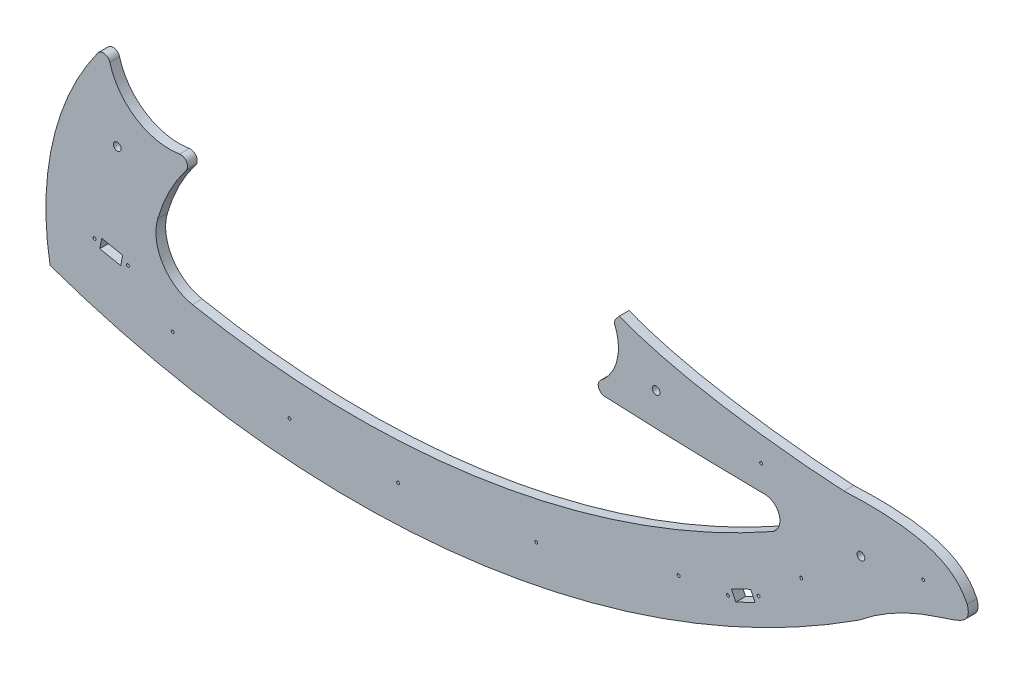
SolidWorks part; units mm, degrees
material "Фанера березовая"
ref_plane "Front Plane" through (0, 0, 0) normal (0, 0, 1) x (1, 0, 0)
ref_plane "Top Plane" through (0, 0, 0) normal (0, 1, 0) x (1, 0, 0)
ref_plane "Right Plane" through (0, 0, 0) normal (1, 0, 0) x (0, 0, -1)
sketch "Несущая боковая" plane through (0, 0, 0) normal (0, 0, 1) x (1, 0, 0)
  line L6 (398.785, -200.6515) -> (-79.2948, -202.7)
  arc A0 (568.0858, 187.1743) -> (604.9253, 231.748) centre (555.0835, 235.431) ccw
  arc A1 (604.9253, 231.748) -> (587.3016, 257.9076) centre (579.4885, 233.6276) ccw
  arc A2 (587.3016, 257.9076) -> (556.344, 256.9224) centre (573.2016, 214.0906) ccw
  arc A4 (-130.7033, -495.9282) -> (-177.7889, -420.4808) centre (-169.1009, -467.4752) ccw
  arc A7 (-130.7033, -495.9282) -> (-181.6944, -712.4375) centre (95.3308, -663.4217) ccw
  arc A8 (-183.8786, -325.353) -> (-177.7889, -420.4808) centre (-186.515, -373.2806) ccw
  arc A9 (-112.9747, -345.6094) -> (-183.8786, -325.353) centre (-193.0224, -491.581) ccw
  arc A11 (23.5507, -511.1423) -> (553.7515, -548.6326) centre (601.0308, 3887.8918) ccw
  arc A12 (7.2112, -514.4863) -> (-70.9864, -615.6156) centre (95.3308, -663.4217) ccw
  arc A13 (-70.9864, -615.6156) -> (-35.2447, -674.0637) centre (-26.3207, -628.4543) ccw
  arc A14 (23.5507, -511.1423) -> (7.2112, -514.4863) centre (20.2245, -536.4807) ccw
  arc A15 (-181.6944, -712.4375) -> (650.1904, -612.5982) centre (132.6498, 184.0228) ccw
  arc A16 (-35.2447, -674.0637) -> (561.2917, -578.0579) centre (132.6498, 184.0228) ccw
  arc A17 (561.2917, -578.0579) -> (553.7515, -548.6326) centre (553.584, -564.3543) ccw
  spline S0 degree 3 poles (556.344, 256.9224) (413.4931, 200.7) (492.8039, -30.4464) (410.7267, -175.5993) knots 0.000401 0.000401 0.000401 0.000401 0.043478 0.043478 0.043478 0.043478
  spline S1 degree 3 poles (410.7267, -175.5993) (407.231, -184.6492) (403.2193, -192.9282) (398.785, -200.6515) knots 0.043478 0.043478 0.043478 0.043478 0.086957 0.086957 0.086957 0.086957
  spline S2 degree 3 poles (-79.2948, -202.7) (-78.5172, -227.7) (-66.7741, -249.7094) (-44.1772, -268.7587) knots 0.130435 0.130435 0.130435 0.130435 0.173913 0.173913 0.173913 0.173913
  spline S3 degree 3 poles (-44.1772, -268.7587) (-12.7058, -245.829) (38.9597, -231.7344) (82.6666, -241.804) knots 0.173913 0.173913 0.173913 0.173913 0.217391 0.217391 0.217391 0.217391
  spline S4 degree 3 poles (82.6666, -241.804) (105.6787, -251.6525) (111.2464, -268.6919) (94.2115, -290.7234) knots 0.217391 0.217391 0.217391 0.217391 0.26087 0.26087 0.26087 0.26087
  spline S5 degree 3 poles (94.2115, -290.7234) (87.1581, -299.8457) (74.9831, -308.4217) (61.0599, -320.5021) knots 0.26087 0.26087 0.26087 0.26087 0.304348 0.304348 0.304348 0.304348
  spline S6 degree 3 poles (61.0599, -320.5021) (47.3806, -331.8412) (34.8832, -345.2678) (22.8705, -359.1067) knots 0.304348 0.304348 0.304348 0.304348 0.347826 0.347826 0.347826 0.347826
  spline S7 degree 3 poles (22.8705, -359.1067) (-5.5844, -391.8897) (-25.5922, -386.6363) (-46.4172, -376.7876) knots 0.347826 0.347826 0.347826 0.347826 0.391304 0.391304 0.391304 0.391304
  spline S8 degree 3 poles (-46.4172, -376.7876) (-71.9902, -366.2219) (-92.784, -356.6815) (-112.9747, -345.6094) knots 0.391304 0.391304 0.391304 0.391304 0.434783 0.434783 0.434783 0.434783
  spline S15 degree 3 poles (650.1904, -612.5982) (721.7263, -555.1366) (771.3742, -572.8028) (761.971, -542.4383) knots 0.695652 0.695652 0.695652 0.695652 0.73913 0.73913 0.73913 0.73913
  spline S16 degree 3 poles (761.971, -542.4383) (749.9881, -518.2511) (723.1034, -500.8362) (635.2399, -505.0064) knots 0.73913 0.73913 0.73913 0.73913 0.782609 0.782609 0.782609 0.782609
  spline S17 degree 3 poles (635.2399, -505.0064) (572.992, -501.9328) (433.5503, -486.7788) (380.9104, -452.9037) knots 0.782609 0.782609 0.782609 0.782609 0.826087 0.826087 0.826087 0.826087
  spline S18 degree 3 poles (380.9104, -452.9037) (364.7659, -442.5143) (356.7862, -430.3638) (361.7026, -416.2609) knots 0.826087 0.826087 0.826087 0.826087 0.869565 0.869565 0.869565 0.869565
  spline S19 degree 3 poles (361.7026, -416.2609) (369.7577, -319.5618) (455.7474, -287.137) (480.2427, -200.3025) knots 0.869565 0.869565 0.869565 0.869565 0.913043 0.913043 0.913043 0.913043
  spline S20 degree 3 poles (480.2427, -200.3025) (553.5443, -5.6015) (495.01, 115.2768) (568.0858, 187.1743) knots 0.913043 0.913043 0.913043 0.913043 0.956522 0.956522 0.956522 0.956522
  spline S31 degree 3 poles (97.4618, -368.9486) (153.6028, -313.7814) (221.4862, -279.2289) (313.8891, -268.7587) knots 0.75 0.75 0.75 0.75 1 1 1 1
  spline S32 degree 3 poles (92.0908, -427.5464) (69.7947, -412.5311) (70.4905, -396.4567) (97.4618, -368.9486) knots 0.5 0.5 0.5 0.5 0.75 0.75 0.75 0.75
  spline S33 degree 3 poles (247.8827, -396.6458) (222.4754, -441.0979) (152.6914, -451.7196) (92.0908, -427.5464) knots 0.25 0.25 0.25 0.25 0.5 0.5 0.5 0.5
  spline S34 degree 3 poles (313.8891, -268.7587) (293.564, -303.651) (262.7411, -332.8991) (247.8827, -396.6458) knots 0 0 0 0 0.25 0.25 0.25 0.25
  dimension "D2" = 48
sketch "Боковая под поперечины" plane through (0, 0, 0) normal (0, 0, 1) x (1, 0, 0)
  line L15 (-159.6049, -346.9107) -> (-207.6507, -344.8161) construction
  line L16 (-207.6507, -344.8161) -> (-218.5759, -409.003)
  line L56 (-207.6507, -344.8161) -> (-159.6963, -346.9068)
  line L57 (-159.6963, -346.9068) -> (-148.2015, -350.3521)
  line L58 (-148.2015, -350.3521) -> (-104.2437, -369.6319)
  line L59 (-104.2437, -369.6319) -> (-95.353, -374.2095)
  line L60 (-95.353, -374.2095) -> (-51.5894, -393.9261)
  line L61 (-51.5894, -393.9261) -> (-42.3459, -397.7417)
  line L62 (-42.3459, -397.7417) -> (2.1537, -415.7357)
  line L63 (2.1537, -415.7357) -> (11.4455, -419.432)
  line L64 (11.4455, -419.432) -> (56.3986, -436.2612)
  line L65 (56.3986, -436.2612) -> (65.8381, -439.5619)
  line L66 (65.8381, -439.5619) -> (111.7403, -453.5971)
  line L67 (111.7403, -453.5971) -> (121.3499, -456.3643)
  line L68 (121.3499, -456.3643) -> (169.2689, -459.1514)
  line L69 (169.2689, -459.1514) -> (179.2066, -458.0374)
  line L70 (179.2066, -458.0374) -> (224.5179, -442.198)
  line L71 (224.5179, -442.198) -> (232.8956, -436.7378)
  line L72 (232.8956, -436.7378) -> (261.7321, -398.3651)
  line L73 (261.7321, -398.3651) -> (267.2053, -389.9959)
  line L74 (267.2053, -389.9959) -> (294.9373, -350.8177)
  line L75 (294.9373, -350.8177) -> (300.8954, -342.7864)
  line L76 (300.8954, -342.7864) -> (330.585, -305.0699)
  line L77 (330.585, -305.0699) -> (336.9867, -297.3877)
  line L78 (336.9867, -297.3877) -> (368.9263, -261.5566)
  line L79 (368.9263, -261.5566) -> (376.1332, -254.6241)
  line L80 (376.1332, -254.6241) -> (406.9239, -217.801)
  line L81 (406.9239, -217.801) -> (412.4436, -209.4624)
  line L82 (412.4436, -209.4624) -> (434.4129, -166.7851)
  line L83 (438.0837, -157.4832) -> (452.6073, -111.7332)
  line L84 (452.6073, -111.7332) -> (454.9033, -102.0003)
  line L85 (454.9033, -102.0003) -> (464.25, -54.9191)
  line L86 (464.25, -54.9191) -> (465.6878, -45.023)
  line L87 (465.6878, -45.023) -> (472.014, 2.5582)
  line L88 (472.014, 2.5582) -> (473.0512, 12.5043)
  line L89 (473.0512, 12.5043) -> (478.3742, 60.2082)
  line L90 (478.3742, 60.2082) -> (479.4656, 70.1485)
  line L91 (479.4656, 70.1485) -> (486.2184, 117.6711)
  line L92 (486.2184, 117.6711) -> (487.9962, 127.5118)
  line L93 (487.9962, 127.5118) -> (500.2801, 173.9134)
  line L94 (500.2801, 173.9134) -> (504.8877, 188.1882)
  line L95 (504.8877, 188.1882) -> (532.6089, 227.3741)
  line L96 (532.6089, 227.3741) -> (546.1164, 235.9502)
  line L97 (546.1164, 235.9502) -> (589.1375, 257.2382)
  line L99 (434.4129, -166.7851) -> (438.0837, -157.4832)
  arc A4 (568.0858, 187.1743) -> (604.9253, 231.748) centre (554.9668, 235.5274) ccw
  arc A7 (604.9253, 231.748) -> (589.1375, 257.2382) centre (579.4223, 233.5866) ccw
  arc A10 (604.9253, 231.748) -> (587.3016, 257.9076) centre (579.4885, 233.6276) ccw construction
  arc A11 (-121.8206, -474.4411) -> (-17.3364, -532.0713) centre (-58.8058, -483.7252) ccw
  arc A12 (7.2112, -514.4863) -> (-17.3364, -532.0713) centre (95.3308, -663.4217) ccw
  arc A13 (23.5507, -511.1423) -> (7.2112, -514.4863) centre (20.2245, -536.4807) ccw
  arc A15 (-121.8206, -474.4411) -> (-177.7889, -420.4808) centre (-169.1009, -467.4752) ccw
  arc A16 (23.5507, -511.1423) -> (352.014, -541.8909) centre (601.0308, 3887.8918) ccw
  arc A17 (-130.7033, -495.9282) -> (-177.7889, -420.4808) centre (-169.1009, -467.4752) ccw construction
  arc A18 (-183.8786, -325.353) -> (-177.7889, -420.4808) centre (-186.515, -373.2806) ccw construction
  arc A19 (-218.5759, -409.003) -> (-177.7889, -420.4808) centre (-186.515, -373.2806) ccw
  arc A20 (23.5507, -511.1423) -> (553.7515, -548.6326) centre (601.0308, 3887.8918) ccw construction
  arc A21 (23.5507, -511.1423) -> (7.2112, -514.4863) centre (20.2245, -536.4807) ccw construction
  arc A22 (7.2112, -514.4863) -> (-70.9864, -615.6156) centre (95.3308, -663.4217) ccw construction
  arc A23 (352.014, -541.8909) -> (380.9104, -452.9037) centre (354.7294, -493.5874) ccw
  spline S13 degree 3 poles (380.9104, -452.9037) (364.7659, -442.5143) (356.7861, -430.3638) (361.7026, -416.2609) knots 0.5 0.5 0.5 0.5 0.533333 0.533333 0.533333 0.533333
  spline S14 degree 3 poles (361.7026, -416.2609) (369.7577, -319.5618) (455.7474, -287.137) (480.2427, -200.3025) knots 0.533333 0.533333 0.533333 0.533333 0.566667 0.566667 0.566667 0.566667
  spline S15 degree 3 poles (480.2427, -200.3025) (553.5444, -5.6014) (495.0101, 115.2768) (568.0858, 187.1743) knots 0.566667 0.566667 0.566667 0.566667 0.6 0.6 0.6 0.6
  point P66 (608.2751, 264.1653)
  point P67 (553.7309, 240.2756)
  point P74 (-221.3236, -344.22)
  dimension "D1" = 48
  dimension "D2" = 12
  dimension "D3" = 10
  dimension "D10" = 16
  dimension "D11" = 15
extrude "Несущая" add sketch "Несущая боковая" along normal blind 10
extrude "Боковая" [suppressed] add sketch "Боковая под поперечины" along normal blind 10
sketch "Sketch3" [suppressed] plane through (0, 0, 0) normal (0, 0, 1) x (1, 0, 0)
  line L0 (546.1164, 235.9502) -> (589.1375, 257.2382) construction
  line L2 (-206.3501, -396.7709) -> (-202.6586, -375.0829)
  line L3 (-216.2083, -395.093) -> (-212.5168, -373.4049)
  line L6 (-216.2083, -395.093) -> (-206.3501, -396.7709)
  line L10 (-207.6507, -344.8161) -> (-194.6631, -345.3823) construction
  line L11 (-207.6507, -344.8161) -> (-208.0863, -354.8066) construction
  line L12 (-159.6963, -346.9068) -> (-160.1319, -356.8973) construction
  line L13 (-208.0863, -354.8066) -> (-195.0986, -355.3728) construction
  line L14 (-194.6631, -345.3823) -> (-195.0986, -355.3728)
  line L15 (-172.684, -346.3405) -> (-173.1195, -356.331)
  line L16 (-173.1195, -356.331) -> (-160.1319, -356.8973) construction
  line L17 (-195.0986, -355.3728) -> (-173.1195, -356.331)
  line L18 (-172.684, -346.3405) -> (-159.6963, -346.9068) construction
  line L19 (-194.6631, -345.3823) -> (-172.684, -346.3405)
  line L37 (-136.2963, -355.5737) -> (-140.3129, -364.7316)
  line L38 (-116.149, -364.4103) -> (-120.1656, -373.5681)
  line L40 (-152.2182, -359.51) -> (-140.3129, -364.7316) construction
  line L41 (-116.149, -364.4103) -> (-104.2437, -369.6319) construction
  line L42 (-140.3129, -364.7316) -> (-120.1656, -373.5681)
  line L43 (-104.2437, -369.6319) -> (-108.2603, -378.7897) construction
  line L44 (-120.1656, -373.5681) -> (-108.2603, -378.7897) construction
  line L45 (-148.2015, -350.3521) -> (-136.2963, -355.5737) construction
  line L46 (-136.2963, -355.5737) -> (-116.149, -364.4103)
  line L47 (-148.2015, -350.3521) -> (-152.2182, -359.51) construction
  line L48 (-104.2437, -369.6319) -> (-148.2015, -350.3521) construction
  line L49 (-63.442, -388.5862) -> (-67.5496, -397.7036)
  line L50 (-83.5003, -379.5494) -> (-63.442, -388.5862)
  line L51 (-83.5003, -379.5494) -> (-87.608, -388.6668)
  line L52 (-63.442, -388.5862) -> (-51.5894, -393.9261) construction
  line L53 (-99.4606, -383.3269) -> (-87.608, -388.6668) construction
  line L54 (-51.5894, -393.9261) -> (-55.697, -403.0436) construction
  line L55 (-95.353, -374.2095) -> (-83.5003, -379.5494) construction
  line L56 (-87.608, -388.6668) -> (-67.5496, -397.7036)
  line L57 (-67.5496, -397.7036) -> (-55.697, -403.0436) construction
  line L58 (-95.353, -374.2095) -> (-99.4606, -383.3269) construction
  line L59 (-34.0427, -411.8858) -> (-13.647, -420.1331)
  line L60 (-30.2939, -402.615) -> (-9.8983, -410.8623)
  line L61 (-42.3459, -397.7417) -> (-30.2939, -402.615) construction
  line L62 (-9.8983, -410.8623) -> (2.1537, -415.7357) construction
  line L63 (-46.0946, -407.0124) -> (-34.0427, -411.8858) construction
  line L64 (-9.8983, -410.8623) -> (-13.647, -420.1331)
  line L65 (-42.3459, -397.7417) -> (-46.0946, -407.0124) construction
  line L66 (-13.647, -420.1331) -> (-1.595, -425.0064) construction
  line L67 (-30.2939, -402.615) -> (-34.0427, -411.8858)
  line L68 (2.1537, -415.7357) -> (-1.595, -425.0064) construction
  line L69 (44.2238, -431.7033) -> (40.7177, -441.0685)
  line L70 (56.3986, -436.2612) -> (52.8925, -445.6264) construction
  line L71 (23.6203, -423.9899) -> (44.2238, -431.7033)
  line L72 (23.6203, -423.9899) -> (20.1142, -433.3551)
  line L73 (7.9394, -428.7972) -> (20.1142, -433.3551) construction
  line L74 (11.4455, -419.432) -> (23.6203, -423.9899) construction
  line L75 (44.2238, -431.7033) -> (56.3986, -436.2612) construction
  line L76 (11.4455, -419.432) -> (7.9394, -428.7972) construction
  line L77 (40.7177, -441.0685) -> (52.8925, -445.6264) construction
  line L78 (20.1142, -433.3551) -> (40.7177, -441.0685)
  line L79 (96.3845, -459.3589) -> (108.8163, -463.1601) construction
  line L80 (65.8381, -439.5619) -> (62.9141, -449.1249) construction
  line L81 (99.3085, -449.7959) -> (96.3845, -459.3589)
  line L82 (78.27, -443.3631) -> (75.346, -452.9261)
  line L83 (65.8381, -439.5619) -> (78.27, -443.3631) construction
  line L84 (62.9141, -449.1249) -> (75.346, -452.9261) construction
  line L85 (99.3085, -449.7959) -> (111.7403, -453.5971) construction
  line L86 (111.7403, -453.5971) -> (108.8163, -463.1601) construction
  line L87 (75.346, -452.9261) -> (96.3845, -459.3589)
  line L88 (78.27, -443.3631) -> (99.3085, -449.7959)
  line L89 (120.7692, -466.3474) -> (133.7473, -467.1023) construction
  line L90 (156.2908, -458.3965) -> (169.2689, -459.1514) construction
  line L91 (133.7473, -467.1023) -> (155.7102, -468.3797)
  line L92 (156.2908, -458.3965) -> (155.7102, -468.3797)
  line L93 (155.7102, -468.3797) -> (168.6882, -469.1345) construction
  line L94 (121.3499, -456.3643) -> (134.3279, -457.1191) construction
  line L95 (134.3279, -457.1191) -> (156.2908, -458.3965)
  line L96 (121.3499, -456.3643) -> (120.7692, -466.3474) construction
  line L97 (134.3279, -457.1191) -> (133.7473, -467.1023)
  line L98 (169.2689, -459.1514) -> (168.6882, -469.1345) construction
  line L99 (215.546, -455.9277) -> (227.8178, -451.6378) construction
  line L100 (191.4784, -453.7475) -> (212.2461, -446.4878)
  line L101 (191.4784, -453.7475) -> (194.7783, -463.1874)
  line L102 (182.5065, -467.4772) -> (194.7783, -463.1874) construction
  line L103 (224.5179, -442.198) -> (227.8178, -451.6378) construction
  line L104 (194.7783, -463.1874) -> (215.546, -455.9277)
  line L105 (179.2066, -458.0374) -> (182.5065, -467.4772) construction
  line L106 (212.2461, -446.4878) -> (224.5179, -442.198) construction
  line L107 (179.2066, -458.0374) -> (191.4784, -453.7475) construction
  line L108 (212.2461, -446.4878) -> (215.546, -455.9277)
  line L109 (248.6998, -432.3528) -> (261.9165, -414.7653)
  line L110 (261.9165, -414.7653) -> (269.7264, -404.3728) construction
  line L111 (240.8899, -442.7454) -> (248.6998, -432.3528) construction
  line L112 (240.7055, -426.3452) -> (248.6998, -432.3528)
  line L113 (253.9222, -408.7577) -> (261.7321, -398.3651) construction
  line L114 (261.7321, -398.3651) -> (269.7264, -404.3728) construction
  line L115 (232.8956, -436.7378) -> (240.7055, -426.3452) construction
  line L116 (240.7055, -426.3452) -> (253.9222, -408.7577)
  line L117 (232.8956, -436.7378) -> (240.8899, -442.7454) construction
  line L118 (253.9222, -408.7577) -> (261.9165, -414.7653)
  line L119 (267.2053, -389.9959) -> (274.7161, -379.3851) construction
  line L120 (267.2053, -389.9959) -> (275.3674, -395.7734) construction
  line L121 (275.3674, -395.7734) -> (282.8782, -385.1626) construction
  line L122 (274.7161, -379.3851) -> (282.8782, -385.1626)
  line L123 (282.8782, -385.1626) -> (295.5887, -367.2059)
  line L124 (287.4266, -361.4284) -> (295.5887, -367.2059)
  line L125 (294.9373, -350.8177) -> (303.0995, -356.5952) construction
  line L126 (295.5887, -367.2059) -> (303.0995, -356.5952) construction
  line L127 (287.4266, -361.4284) -> (294.9373, -350.8177) construction
  line L128 (274.7161, -379.3851) -> (287.4266, -361.4284)
  line L129 (330.4016, -321.4701) -> (338.4426, -311.2553) construction
  line L130 (316.7939, -338.7569) -> (330.4016, -321.4701)
  line L131 (308.9363, -332.5715) -> (322.5441, -315.2848)
  line L132 (300.8954, -342.7864) -> (308.9363, -332.5715) construction
  line L133 (300.8954, -342.7864) -> (308.753, -348.9717) construction
  line L134 (308.9363, -332.5715) -> (316.7939, -338.7569)
  line L135 (322.5441, -315.2848) -> (330.4016, -321.4701)
  line L136 (308.753, -348.9717) -> (316.7939, -338.7569) construction
  line L137 (330.585, -305.0699) -> (338.4426, -311.2553) construction
  line L138 (322.5441, -315.2848) -> (330.585, -305.0699) construction
  line L139 (336.9867, -297.3877) -> (344.4515, -304.0418) construction
  line L140 (360.276, -271.2609) -> (367.7408, -277.915)
  line L141 (367.7408, -277.915) -> (376.3911, -268.2107) construction
  line L142 (344.4515, -304.0418) -> (353.1018, -294.3375) construction
  line L143 (353.1018, -294.3375) -> (367.7408, -277.915)
  line L144 (336.9867, -297.3877) -> (345.637, -287.6834) construction
  line L145 (368.9263, -261.5566) -> (376.3911, -268.2107) construction
  line L146 (360.276, -271.2609) -> (368.9263, -261.5566) construction
  line L147 (345.637, -287.6834) -> (360.276, -271.2609)
  line L148 (345.637, -287.6834) -> (353.1018, -294.3375)
  line L149 (406.2562, -234.1886) -> (414.5953, -224.2157) construction
  line L150 (398.5847, -227.7739) -> (406.2562, -234.1886)
  line L151 (392.1438, -251.0659) -> (406.2562, -234.1886)
  line L152 (383.8047, -261.0388) -> (392.1438, -251.0659) construction
  line L153 (406.9239, -217.801) -> (414.5953, -224.2157) construction
  line L154 (376.1332, -254.6241) -> (384.4724, -244.6512) construction
  line L155 (376.1332, -254.6241) -> (383.8047, -261.0388) construction
  line L156 (398.5847, -227.7739) -> (406.9239, -217.801) construction
  line L157 (384.4724, -244.6512) -> (392.1438, -251.0659)
  line L158 (384.4724, -244.6512) -> (398.5847, -227.7739)
  line L159 (437.354, -182.9205) -> (443.304, -171.3621) construction
  line L160 (428.4629, -178.3436) -> (434.4129, -166.7851) construction
  line L161 (428.4629, -178.3436) -> (437.354, -182.9205)
  line L162 (418.3936, -197.904) -> (427.2847, -202.4809)
  line L163 (427.2847, -202.4809) -> (437.354, -182.9205)
  line L164 (412.4436, -209.4624) -> (421.3346, -214.0393) construction
  line L165 (421.3346, -214.0393) -> (427.2847, -202.4809) construction
  line L166 (434.4129, -166.7851) -> (443.304, -171.3621) construction
  line L167 (418.3936, -197.904) -> (428.4629, -178.3436)
  line L168 (412.4436, -209.4624) -> (418.3936, -197.904) construction
  line L169 (447.6149, -160.509) -> (451.5484, -148.1183) construction
  line L170 (448.6738, -124.1238) -> (452.6073, -111.7332) construction
  line L171 (442.0172, -145.0926) -> (451.5484, -148.1183)
  line L172 (448.6738, -124.1238) -> (458.205, -127.1496)
  line L173 (438.0837, -157.4832) -> (442.0172, -145.0926) construction
  line L174 (458.205, -127.1496) -> (462.1385, -114.7589) construction
  line L175 (442.0172, -145.0926) -> (448.6738, -124.1238)
  line L176 (452.6073, -111.7332) -> (462.1385, -114.7589) construction
  line L177 (438.0837, -157.4832) -> (447.6149, -160.509) construction
  line L178 (451.5484, -148.1183) -> (458.205, -127.1496)
  line L179 (-51.5894, -393.9261) -> (-95.353, -374.2095) construction
  line L180 (2.1537, -415.7357) -> (-42.3459, -397.7417) construction
  line L181 (56.3986, -436.2612) -> (11.4455, -419.432) construction
  line L182 (368.9263, -261.5566) -> (336.9867, -297.3877) construction
  line L183 (406.9239, -217.801) -> (376.1332, -254.6241) construction
  line L184 (434.4129, -166.7851) -> (412.4436, -209.4624) construction
  line L185 (452.6073, -111.7332) -> (438.0837, -157.4832) construction
  line L186 (464.7118, -103.9476) -> (467.2432, -91.1964) construction
  line L187 (457.4347, -89.2492) -> (461.7186, -67.6703)
  line L188 (454.9033, -102.0003) -> (457.4347, -89.2492) construction
  line L189 (457.4347, -89.2492) -> (467.2432, -91.1964)
  line L190 (461.7186, -67.6703) -> (464.25, -54.9191) construction
  line L191 (454.9033, -102.0003) -> (464.7118, -103.9476) construction
  line L192 (464.25, -54.9191) -> (474.0586, -56.8664) construction
  line L193 (467.2432, -91.1964) -> (471.5272, -69.6175)
  line L194 (461.7186, -67.6703) -> (471.5272, -69.6175)
  line L195 (471.5272, -69.6175) -> (474.0586, -56.8664) construction
  line L196 (467.4011, -32.1364) -> (470.3006, -10.3284)
  line L197 (465.6878, -45.023) -> (467.4011, -32.1364) construction
  line L198 (472.014, 2.5582) -> (481.9268, 1.2403) construction
  line L199 (477.3139, -33.4544) -> (480.2134, -11.6463)
  line L200 (470.3006, -10.3284) -> (472.014, 2.5582) construction
  line L201 (480.2134, -11.6463) -> (481.9268, 1.2403) construction
  line L202 (465.6878, -45.023) -> (475.6006, -46.341) construction
  line L203 (467.4011, -32.1364) -> (477.3139, -33.4544)
  line L204 (470.3006, -10.3284) -> (480.2134, -11.6463)
  line L205 (475.6006, -46.341) -> (477.3139, -33.4544) construction
  line L206 (473.0512, 12.5043) -> (474.4928, 25.4241) construction
  line L207 (474.4928, 25.4241) -> (476.9325, 47.2884)
  line L208 (473.0512, 12.5043) -> (482.9895, 11.3953) construction
  line L209 (486.8708, 46.1795) -> (488.3125, 59.0993) construction
  line L210 (476.9325, 47.2884) -> (486.8708, 46.1795)
  line L211 (474.4928, 25.4241) -> (484.4311, 24.3152)
  line L212 (482.9895, 11.3953) -> (484.4311, 24.3152) construction
  line L213 (484.4311, 24.3152) -> (486.8708, 46.1795)
  line L214 (478.3742, 60.2082) -> (488.3125, 59.0993) construction
  line L215 (476.9325, 47.2884) -> (478.3742, 60.2082) construction
  line L216 (486.2184, 117.6711) -> (496.119, 116.2643) construction
  line L217 (481.2945, 83.0192) -> (484.3895, 104.8004)
  line L218 (491.195, 81.6124) -> (494.2901, 103.3936)
  line L219 (494.2901, 103.3936) -> (496.119, 116.2643) construction
  line L220 (484.3895, 104.8004) -> (486.2184, 117.6711) construction
  line L221 (484.3895, 104.8004) -> (494.2901, 103.3936)
  line L222 (479.4656, 70.1485) -> (481.2945, 83.0192) construction
  line L223 (479.4656, 70.1485) -> (489.3661, 68.7417) construction
  line L224 (481.2945, 83.0192) -> (491.195, 81.6124)
  line L225 (489.3661, 68.7417) -> (491.195, 81.6124) construction
  line L226 (500.2801, 173.9134) -> (509.9471, 171.3543) construction
  line L227 (497.6632, 124.9527) -> (500.9901, 137.5198) construction
  line L228 (491.3231, 140.0789) -> (496.9532, 161.3463)
  line L229 (506.6202, 158.7872) -> (509.9471, 171.3543) construction
  line L230 (487.9962, 127.5118) -> (491.3231, 140.0789) construction
  line L231 (487.9962, 127.5118) -> (497.6632, 124.9527) construction
  line L232 (491.3231, 140.0789) -> (500.9901, 137.5198)
  line L233 (496.9532, 161.3463) -> (506.6202, 158.7872)
  line L234 (500.9901, 137.5198) -> (506.6202, 158.7872)
  line L235 (496.9532, 161.3463) -> (500.2801, 173.9134) construction
  line L236 (512.3955, 198.8011) -> (525.1011, 216.7613)
  line L237 (504.8877, 188.1882) -> (513.0514, 182.413) construction
  line L238 (525.1011, 216.7613) -> (532.6089, 227.3741) construction
  line L239 (512.3955, 198.8011) -> (520.5593, 193.0258)
  line L240 (525.1011, 216.7613) -> (533.2648, 210.986)
  line L241 (532.6089, 227.3741) -> (540.7726, 221.5989) construction
  line L242 (504.8877, 188.1882) -> (512.3955, 198.8011) construction
  line L243 (533.2648, 210.986) -> (540.7726, 221.5989) construction
  line L244 (513.0514, 182.413) -> (520.5593, 193.0258) construction
  line L245 (520.5593, 193.0258) -> (533.2648, 210.986)
  line L246 (589.1375, 257.2382) -> (593.5725, 248.2755) construction
  line L247 (557.7679, 241.7157) -> (562.2029, 232.7529)
  line L248 (546.1164, 235.9502) -> (557.7679, 241.7157) construction
  line L249 (577.4859, 251.4727) -> (581.9209, 242.51)
  line L250 (581.9209, 242.51) -> (593.5725, 248.2755) construction
  line L251 (557.7679, 241.7157) -> (577.4859, 251.4727)
  line L252 (546.1164, 235.9502) -> (550.5514, 226.9874) construction
  line L253 (562.2029, 232.7529) -> (581.9209, 242.51)
  line L254 (577.4859, 251.4727) -> (589.1375, 257.2382) construction
  line L255 (550.5514, 226.9874) -> (562.2029, 232.7529) construction
  line L256 (464.25, -54.9191) -> (454.9033, -102.0003) construction
  line L257 (472.014, 2.5582) -> (465.6878, -45.023) construction
  line L258 (486.2184, 117.6711) -> (479.4656, 70.1485) construction
  line L259 (500.2801, 173.9134) -> (487.9962, 127.5118) construction
  line L260 (487.9962, 127.5118) -> (486.2184, 117.6711) construction
  line L261 (532.6089, 227.3741) -> (504.8877, 188.1882) construction
  line L262 (504.8877, 188.1882) -> (500.2801, 173.9134) construction
  line L264 (-212.5168, -373.4049) -> (-202.6586, -375.0829)
  line L269 (-207.6507, -344.8161) -> (-218.5759, -409.003) construction
  point P1 (-214.3626, -384.2489)
  dimension "D1" = 40
  dimension "D2" = 10
  dimension "D3" = 22
extrude "Шипы" [suppressed] cut sketch "Sketch3" along normal through all
sketch "Sketch4" [suppressed] plane through (0, 0, 10) normal (0, 0, 1) x (1, 0, 0)
  line L0 (-208.4348, -362.799) -> (-221.0097, -388.653) construction
  line L1 (-221.0097, -388.653) -> (-207.6507, -344.8161) construction
  line L2 (-207.6507, -344.8161) -> (-208.4348, -362.799) construction
  line L4 (-217.7838, -439.8154) -> (-237.4507, -429.7729) construction
  line L5 (-237.4507, -429.7729) -> (-240.164, -452.0896) construction
  line L6 (-240.164, -452.0896) -> (-201.8347, -418.7702) construction
  arc A1 (-218.5759, -409.003) -> (-177.7889, -420.4808) centre (-186.515, -373.2806) ccw construction
extrude "Излишки" [suppressed] cut sketch "Sketch4" against normal up to next
sketch "Sketch5" plane through (0, 0, 10) normal (0, 0, 1) x (1, 0, 0)
  line L1 (40.6613, -192.1859) -> (90.6608, -191.9717)
  line L2 (40.6613, -192.1859) -> (40.7041, -202.1858)
  line L3 (40.7041, -202.1858) -> (90.7037, -201.9716)
  line L4 (90.6608, -191.9717) -> (90.7037, -201.9716)
  line L5 (398.785, -200.6515) -> (-79.2948, -202.7) construction
  line L6 (240.6594, -191.329) -> (290.659, -191.1147)
  line L7 (240.6594, -191.329) -> (240.7023, -201.3289)
  line L8 (240.7023, -201.3289) -> (290.7018, -201.1146)
  line L9 (290.659, -191.1147) -> (290.7018, -201.1146)
  dimension "D1" = 10
  dimension "D2" = 150
  dimension "D3" = 120
  dimension "D4" = 50
extrude "Шипы на подлокотниках" [suppressed] add sketch "Sketch5" against normal up to surface (10 mm away) up to face at (172.6744, -583.2036, 0)
sketch "Sketch6" plane through (0, 0, 10) normal (0, 0, 1) x (1, 0, 0)
  line L0 (-139.8462, -659.6686) -> (-141.8053, -669.4748)
  line L1 (-141.8053, -669.4748) -> (-127.0959, -672.4134)
  line L2 (-127.0959, -672.4134) -> (-125.1369, -662.6072)
  line L3 (-125.1369, -662.6072) -> (-139.8462, -659.6686)
  line L4 (-127.0959, -672.4134) -> (-112.3866, -675.352) construction
  line L5 (-112.3866, -675.352) -> (-110.4276, -665.5457)
  line L6 (-110.4276, -665.5457) -> (-95.7182, -668.4843)
  line L7 (-95.7182, -668.4843) -> (-97.6773, -678.2905)
  line L8 (-97.6773, -678.2905) -> (-112.3866, -675.352)
  line L9 (-119.7413, -673.8827) -> (-117.7822, -664.0765) construction
  line L10 (-125.1369, -662.6072) -> (-110.4276, -665.5457) construction
  line L11 (-126.1164, -667.5103) -> (-111.4071, -670.4489) construction
  line L12 (522.6672, -648.5899) -> (536.3744, -642.4979) construction
  line L13 (554.1429, -645.5439) -> (540.4358, -651.636)
  line L14 (533.5822, -654.682) -> (529.5208, -645.5439) construction
  line L15 (522.6672, -648.5899) -> (508.96, -654.682)
  line L16 (513.0214, -663.8201) -> (526.7286, -657.728)
  line L17 (526.7286, -657.728) -> (540.4358, -651.636) construction
  line L18 (526.7286, -657.728) -> (522.6672, -648.5899)
  line L19 (540.4358, -651.636) -> (536.3744, -642.4979)
  line L20 (524.6979, -653.159) -> (538.4051, -647.0669) construction
  line L21 (550.0815, -636.4058) -> (554.1429, -645.5439)
  line L22 (508.96, -654.682) -> (513.0214, -663.8201)
  line L23 (536.3744, -642.4979) -> (550.0815, -636.4058)
  circle A2 centre (531.5515, -650.113) radius 1.5
  circle A4 centre (-118.7618, -668.9796) radius 1.5
  dimension "D1" = 10
  dimension "D4" = 3
  dimension "D6" = 3
  dimension "D2" = 15
  dimension "D5" = 15
extrude "Под ребра жесткости" [suppressed] cut sketch "Sketch6" against normal up to next
sketch "Sketch10" plane through (0, 0, 10) normal (0, 0, 1) x (1, 0, 0)
  line L0 (-160.015, -545.337) -> (-65.0834, -598.5055) construction
  line L1 (-62.9558, -479.5752) -> (-54.6558, -487.8752) construction
  line L2 (-62.9558, -479.5752) -> (-54.6558, -479.5752)
  line L3 (-62.9558, -479.5752) -> (-62.9558, -487.8752)
  line L4 (-62.9558, -487.8752) -> (-54.6558, -487.8752)
  line L5 (-54.6558, -479.5752) -> (-54.6558, -487.8752)
  line L6 (-54.6558, -479.5752) -> (-62.9558, -487.8752) construction
  line L7 (-116.6992, -567.7712) -> (-108.3992, -576.0712) construction
  line L8 (-116.6992, -567.7712) -> (-108.3992, -567.7712)
  line L9 (-116.6992, -567.7712) -> (-116.6992, -576.0712)
  line L10 (-116.6992, -576.0712) -> (-108.3992, -576.0712)
  line L11 (-108.3992, -567.7712) -> (-108.3992, -576.0712)
  line L12 (-108.3992, -567.7712) -> (-116.6992, -576.0712) construction
  line L13 (648.5083, -550.2053) -> (656.8083, -558.5053) construction
  line L14 (648.5083, -550.2053) -> (656.8083, -550.2053)
  line L15 (648.5083, -550.2053) -> (648.5083, -558.5053)
  line L16 (648.5083, -558.5053) -> (656.8083, -558.5053)
  line L17 (656.8083, -550.2053) -> (656.8083, -558.5053)
  line L18 (656.8083, -550.2053) -> (648.5083, -558.5053) construction
  line L19 (339.781, -487.9124) -> (348.081, -496.2124) construction
  line L20 (339.781, -487.9124) -> (348.081, -487.9124)
  line L21 (339.781, -487.9124) -> (339.781, -496.2124)
  line L22 (339.781, -496.2124) -> (348.081, -496.2124)
  line L23 (348.081, -487.9124) -> (348.081, -496.2124)
  line L24 (348.081, -487.9124) -> (339.781, -496.2124) construction
  line L25 (578.9469, 219.618) -> (587.2469, 211.318) construction
  line L26 (578.9469, 219.618) -> (587.2469, 219.618)
  line L27 (578.9469, 219.618) -> (578.9469, 211.318)
  line L28 (578.9469, 211.318) -> (587.2469, 211.318)
  line L29 (587.2469, 219.618) -> (587.2469, 211.318)
  line L30 (587.2469, 219.618) -> (578.9469, 211.318) construction
  line L31 (437.7655, -507.8881) -> (446.0655, -516.1881) construction
  line L32 (437.7655, -507.8881) -> (446.0655, -507.8881)
  line L33 (437.7655, -507.8881) -> (437.7655, -516.1881)
  line L34 (437.7655, -516.1881) -> (446.0655, -516.1881)
  line L35 (446.0655, -507.8881) -> (446.0655, -516.1881)
  line L36 (446.0655, -507.8881) -> (437.7655, -516.1881) construction
  line L37 (446.0655, -478.1967) -> (437.7655, -545.8796) construction
  circle A0 centre (-58.8058, -483.7252) radius 4 construction
  circle A1 centre (343.931, -492.0624) radius 4 construction
  circle A2 centre (583.0969, 215.468) radius 4 construction
  circle A3 centre (-112.5492, -571.9212) radius 4 construction
  circle A4 centre (652.6583, -554.3553) radius 4 construction
  arc A5 (-130.7033, -495.9282) -> (-181.6944, -712.4375) centre (95.3308, -663.4217) ccw construction
  arc A6 (7.2112, -514.4863) -> (-70.9864, -615.6156) centre (95.3308, -663.4217) ccw construction
  circle A7 centre (441.9155, -512.0381) radius 4 construction
  arc A8 (23.5507, -511.1423) -> (553.7515, -548.6326) centre (601.0308, 3887.8918) ccw construction
  spline S0 degree 3 poles (635.2399, -505.0064) (572.992, -501.9328) (433.5503, -486.7788) (380.9104, -452.9037) knots 0.782609 0.782609 0.782609 0.782609 0.826087 0.826087 0.826087 0.826087 construction
  point P18 (-58.8058, -483.7252)
  point P19 (-112.5492, -571.9212)
  point P28 (652.6583, -554.3553)
  point P40 (343.931, -492.0624)
  point P41 (583.0969, 215.468)
  point P49 (441.9155, -512.0381)
  point P52 (441.9155, -512.0381)
  dimension "D1" = 8
  dimension "D2" = 8.3
  dimension "D3" = 8.3
  dimension "D4" = 100
extrude "Под болты М8 в несущей" [suppressed] cut sketch "Sketch10" against normal blind 10
sketch "Sketch7" [suppressed] plane through (0, 0, 10) normal (0, 0, 1) x (1, 0, 0)
  line L0 (567.6269, 246.5942) -> (583.0969, 215.468) construction
  line L1 (577.4859, 251.4727) -> (557.7679, 241.7157) construction
  circle A0 centre (583.0969, 215.468) radius 10 construction
  circle A1 centre (583.0969, 215.468) radius 4
  circle A2 centre (343.931, -492.0624) radius 4
  circle A3 centre (-58.8058, -483.7252) radius 4
  arc A5 (-121.8206, -474.4411) -> (-17.3364, -532.0713) centre (-58.8058, -483.7252) ccw construction
  dimension "D1" = 8
  dimension "D2" = 20
extrude "Под болты М8 в боковой" [suppressed] cut sketch "Sketch7" against normal blind 20
sketch "Sketch9" [suppressed] plane through (0, 0, 10) normal (0, 0, 1) x (1, 0, 0)
  line L0 (343.931, -492.0624) -> (255.3082, -423.5591) construction
  line L1 (248.6998, -432.3528) -> (261.9165, -414.7653) construction
  circle A1 centre (-165.7, -390.7733) radius 1.5
  circle A2 centre (-19.0866, -469.5934) radius 1.5 construction
  circle A3 centre (116.1327, -506.7832) radius 1.5
  circle A4 centre (265.4187, -506.7832) radius 1.5
  circle A5 centre (335.948, -380.5609) radius 1.5
  circle A6 centre (431.4673, -250.6533) radius 1.5
  circle A7 centre (486.9514, -124.9981) radius 1.5
  circle A8 centre (512.1042, 60.8892) radius 1.5
  circle A9 centre (285.9819, -447.2691) radius 1.5
  dimension "D1" = 3
extrude "Под шурупы в боковой" [suppressed] cut sketch "Sketch9" against normal up to next
sketch "Sketch11" plane through (0, 0, 10) normal (0, 0, 1) x (1, 0, 0)
  line L0 (-41.7058, -557.7439) -> (389.0009, -543.8153)
  line L2 (-132.5999, -498.5185) -> (-477.3198, -249.1207)
  line L3 (-477.3198, -249.1207) -> (641.9014, 366.4652)
  line L4 (641.9014, 366.4652) -> (806.4928, -337.8987)
  line L5 (806.4928, -337.8987) -> (445.1298, -438.4405)
  line L8 (-128.5201, -661.6763) -> (-130.5771, -671.9729)
  line L12 (-109.0034, -676.2828) -> (-106.9464, -665.9863)
  line L13 (-130.5771, -671.9729) -> (-109.0034, -676.2828)
  line L14 (-106.9464, -665.9863) -> (-128.5201, -661.6763)
  line L15 (-117.7333, -663.8313) -> (-119.7903, -674.1278) construction
  line L16 (-129.5486, -666.8246) -> (-107.9749, -671.1345) construction
  line L21 (519.363, -650.1678) -> (523.9282, -659.6234)
  line L23 (543.74, -650.0581) -> (539.1747, -640.6025)
  line L24 (523.9282, -659.6234) -> (543.74, -650.0581)
  line L27 (539.1747, -640.6025) -> (519.363, -650.1678)
  line L29 (237.3954, -684.0379) -> (245.8495, -759.184) construction
  line L30 (-120.0533, -668.7215) -> (-49151.1969, 9126.5302) construction
  line L31 (529.2689, -645.3851) -> (533.8341, -654.8408) construction
  line L32 (521.6456, -654.8956) -> (541.4574, -645.3303) construction
  line L33 (530.5622, -650.5906) -> (-37026.229, -18783.254) construction
  arc A0 (384.9612, -531.3583) -> (399.6262, -475.5629) centre (354.7294, -493.5874) ccw
  arc A1 (-120.1832, -500.7506) -> (-48.3933, -546.5634) centre (-58.8058, -483.7252) ccw
  arc A2 (-121.8206, -474.4411) -> (-17.3364, -532.0713) centre (-58.8058, -483.7252) ccw construction
  arc A3 (352.014, -541.8909) -> (380.9104, -452.9037) centre (354.7294, -493.5874) ccw construction
  arc A5 (-120.1832, -500.7506) -> (-132.5999, -498.5185) centre (-126.9285, -502.6217) ccw
  arc A6 (401.9166, -467.3592) -> (399.6262, -475.5629) centre (406.1223, -472.955) ccw
  arc A7 (384.9612, -531.3583) -> (389.0009, -543.8153) centre (389.3355, -536.8233) ccw
  arc A8 (23.5507, -511.1423) -> (553.7515, -548.6326) centre (601.0308, 3887.8918) ccw construction
  arc A9 (-41.7058, -557.7439) -> (-48.3933, -546.5634) centre (-47.249, -553.4692) ccw
  arc A10 (7.2112, -514.4863) -> (-70.9864, -615.6156) centre (95.3308, -663.4217) ccw construction
  arc A11 (-130.7033, -495.9282) -> (-181.6944, -712.4375) centre (95.3308, -663.4217) ccw construction
  arc A12 (445.1298, -438.4405) -> (401.9166, -467.3592) centre (467.3913, -518.4518) ccw
  circle A13 centre (-118.7618, -668.9796) radius 1.5 construction
  circle A14 centre (-118.7618, -668.9796) radius 1.5 construction
  circle A15 centre (531.5515, -650.113) radius 1.5 construction
  circle A16 centre (531.5515, -650.113) radius 1.5 construction
  circle A17 centre (-112.5492, -571.9212) radius 4
  circle A18 centre (652.6583, -554.3553) radius 4
  circle A19 centre (652.6583, -554.3553) radius 4 construction
  circle A20 centre (-112.5492, -571.9212) radius 4 construction
  circle A21 centre (132.6498, 184.0228) radius 912.1663 construction
  arc A22 (-181.6944, -712.4375) -> (650.1904, -612.5982) centre (132.6498, 184.0228) ccw construction
  arc A23 (-35.2447, -674.0637) -> (561.2917, -578.0579) centre (132.6498, 184.0228) ccw construction
  circle A24 centre (-55.6293, -708.5009) radius 1.5
  circle A25 centre (64.6121, -725.6026) radius 1.5
  circle A26 centre (176.3683, -727.0953) radius 1.5
  circle A27 centre (318.5821, -708.9927) radius 1.5
  circle A28 centre (465.0308, -665.4302) radius 1.5
  circle A29 centre (591.2442, -604.4813) radius 1.5
  circle A30 centre (-132.5999, -530.8006) radius 1.5 construction
  circle A31 centre (-65.9031, -561.841) radius 1.5 construction
  circle A32 centre (417.14, -488.0696) radius 1.5 construction
  circle A33 centre (397.834, -530.8006) radius 1.5 construction
  circle A34 centre (549.9426, -522.8301) radius 1.5
  circle A35 centre (716.7021, -543.294) radius 1.5
  circle A36 centre (441.9155, -512.0381) radius 4
  circle A37 centre (441.9155, -512.0381) radius 4 construction
  circle A39 centre (547.3108, -642.5042) radius 1.5
  circle A41 centre (-101.6009, -672.4079) radius 1.5
  circle A42 centre (-135.9227, -665.5512) radius 1.5
  circle A43 centre (515.7921, -657.7217) radius 1.5
  spline S3 degree 3 poles (635.2399, -505.0064) (572.992, -501.9328) (433.5503, -486.7788) (380.9104, -452.9037) knots 0.782609 0.782609 0.782609 0.782609 0.826087 0.826087 0.826087 0.826087 construction
  point P43 (-118.7618, -668.9796)
  point P66 (531.5515, -650.113)
  point P85 (241.6225, -721.6109)
  point P121 (-117.7333, -663.8313)
  point P122 (-100.964, -672.5351)
  point P124 (-107.9749, -671.1345)
  point P126 (-129.5486, -666.8246)
  point P130 (529.2689, -645.3851)
  point P132 (541.4574, -645.3303)
  point P134 (521.6456, -654.8956)
  dimension "D1" = 7
  dimension "D3" = 3
  dimension "D5" = 3
  dimension "D9" = 3
  dimension "D2" = 10.5
  dimension "D4" = 22
  dimension "D6" = 17.5
  dimension "D7" = 22
  dimension "D8" = 10.5
  dimension "D10" = 17.5
extrude "Усиление несущей спереди" cut sketch "Sketch11" against normal up to next
sketch "Эскиз1" [suppressed] plane through (0, 0, 10) normal (0, 0, 1) x (1, 0, 0)
  arc A0 (-95.5358, -456.7447) -> (-162.1578, -550.0855) centre (95.3308, -663.4217) ccw
  arc A1 (-22.0758, -536.2898) -> (-64.3311, -596.6766) centre (95.3308, -663.4217) ccw
  arc A2 (-130.7033, -495.9282) -> (-181.6944, -712.4375) centre (95.3308, -663.4217) ccw construction
  arc A3 (7.2112, -514.4863) -> (-70.9864, -615.6156) centre (95.3308, -663.4217) ccw construction
  arc A4 (-22.0758, -536.2898) -> (-95.5358, -456.7447) centre (-58.8058, -496.5172) ccw
  arc A5 (-162.1578, -550.0855) -> (-61.7267, -590.7596) centre (-112.5492, -571.9212) ccw
extrude "Усилительный элемент передний" [suppressed] cut sketch "Эскиз1" against normal through all flip side to cut
sketch "Эскиз2" [suppressed] plane through (0, 0, 10) normal (0, 0, 1) x (1, 0, 0)
  line L0 (-62.9558, -479.5752) -> (-54.6558, -487.8752) construction
  line L1 (-160.015, -545.337) -> (-65.0834, -598.5055) construction
  circle A0 centre (-58.8058, -483.7252) radius 4
  circle A1 centre (-112.5492, -571.9212) radius 4
  circle A2 centre (-112.5492, -571.9212) radius 4 construction
  circle A3 centre (-58.8058, -483.7252) radius 4 construction
extrude "Под болты в переднем усилительном элементе" [suppressed] cut sketch "Эскиз2" against normal through all
sketch "Эскиз3" [suppressed] plane through (0, 0, 10) normal (0, 0, 1) x (1, 0, 0)
  line L0 (437.7655, -512.0381) -> (446.0655, -512.0381) construction
  arc A0 (352.0141, -541.8909) -> (440.1192, -545.9656) centre (601.0308, 3887.8918) ccw
  arc A1 (440.1192, -545.9656) -> (449.6845, -479.1271) centre (441.3505, -512.0381) ccw
  arc A2 (380.9104, -452.9037) -> (352.0141, -541.8909) centre (354.7295, -493.5874) ccw
  arc A3 (23.5507, -511.1423) -> (553.7515, -548.6326) centre (601.0308, 3887.8918) ccw construction
  spline S0 degree 3 poles (635.2399, -505.0064) (572.992, -501.9328) (433.5503, -486.7788) (380.9104, -452.9037) knots 0.782609 0.782609 0.782609 0.782609 0.826087 0.826087 0.826087 0.826087
  spline S1 degree 3 poles (380.9104, -452.9037) (364.7659, -442.5143) (356.7862, -430.3638) (361.7026, -416.2609) knots 0.826087 0.826087 0.826087 0.826087 0.869565 0.869565 0.869565 0.869565
extrude "Усилительный элемент задний" [suppressed] cut sketch "Эскиз3" against normal through all flip side to cut
sketch "Эскиз4" [suppressed] plane through (0, 0, 10) normal (0, 0, 1) x (1, 0, 0)
  line L0 (348.081, -487.9124) -> (339.781, -496.2124) construction
  circle A0 centre (441.9155, -512.0381) radius 4
  circle A1 centre (343.931, -492.0624) radius 4
  circle A2 centre (343.931, -492.0624) radius 4 construction
  circle A3 centre (441.9155, -512.0381) radius 4 construction
extrude "Под болты в заднем усилительном элементе" [suppressed] cut sketch "Эскиз4" against normal through all
fillet "Скругление1" [suppressed] radius 10
equation "\"mm\"=20"
